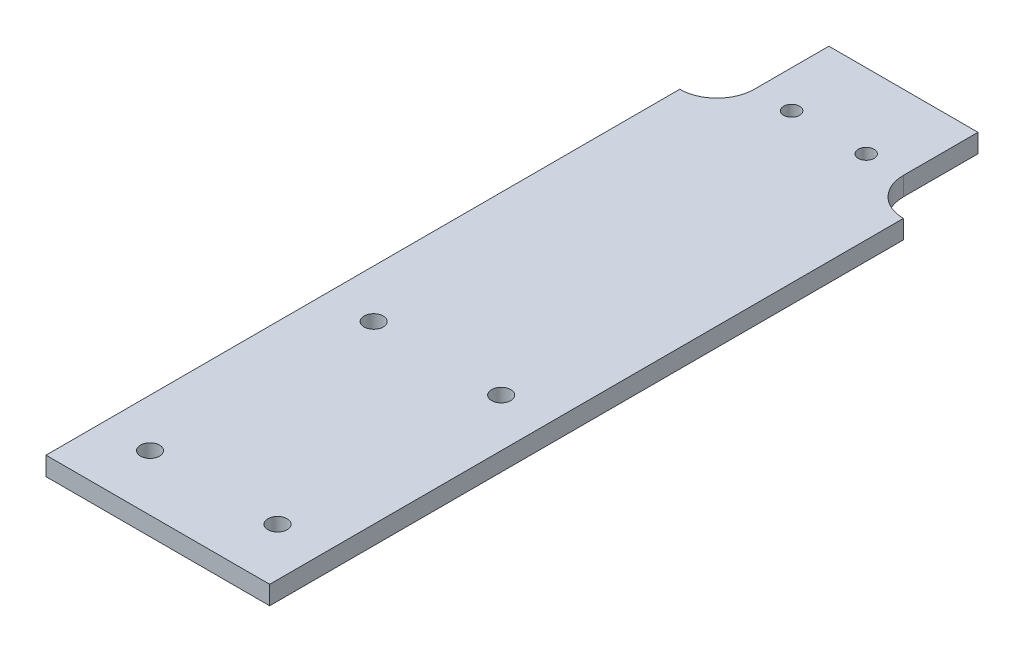
SolidWorks part; units mm, degrees
material "6061 Alloy"
ref_plane "Front Plane" through (0, 0, 0) normal (0, 0, 1) x (1, 0, 0)
ref_plane "Top Plane" through (0, 0, 0) normal (0, 1, 0) x (1, 0, 0)
ref_plane "Right Plane" through (0, 0, 0) normal (1, 0, 0) x (0, 0, -1)
sketch "Sketch1" plane through (0, 0, 0) normal (0, 1, 0) x (1, 0, 0)
  line L1 (-19.05, 50.8) -> (19.05, 50.8)
  line L2 (-19.05, 50.8) -> (-19.05, -76.2)
  line L3 (-19.05, -76.2) -> (19.05, -76.2)
  line L4 (19.05, 50.8) -> (19.05, -76.2)
  dimension "D1" = 38.1
  dimension "D2" = 19.05
  dimension "D3" = 76.2
  dimension "D4" = 50.8
extrude "Extrude1" add sketch "Sketch1" along normal blind 3.175
hole_wizard "#4 Clearance Hole1" positions "3DSketch1" profile "Sketch3" hole size "#4" standard "Ansi Inch"
sketch3d "3DSketch1"
  line L0 (-19.05, 0, 28.575) -> (19.05, 0, 28.575) construction
  line L1 (-19.05, 0, -50.8) -> (-19.05, 0, 76.2) construction
  line L2 (19.05, 0, 76.2) -> (19.05, 0, -50.8) construction
  line L4 (0, 0, 28.575) -> (0, 0, 76.2) construction
  line L5 (-19.05, 0, 76.2) -> (19.05, 0, 76.2) construction
  line L7 (19.05, 0, -50.8) -> (-19.05, 0, -50.8) construction
  line L8 (-19.05, 0, 66.675) -> (19.05, 0, 66.675) construction
  point P0 (-10.8585, 0, 28.575)
  point P2 (10.8585, 0, 28.575)
  point P26 (-10.8585, 0, 66.675)
  point P28 (10.8585, 0, 66.675)
  dimension "D1" = 21.717
  dimension "D2" = 10.8585
  dimension "D3" = 79.375
  dimension "D4" = 38.1
sketch "Sketch3" plane through (-10.8585, 0, 28.575) normal (1, 0, 0) x (0, 0, -1)
  line L0 (0, 0) -> (0, 102.5806)
  line L1 (0, 102.5806) -> (1.6319, 101.6)
  line L2 (1.6319, 101.6) -> (1.6319, 0)
  line L5 (1.6319, 0) -> (0, 0)
  line L10 (0, 102.5806) -> (-1.632, 101.6) construction
  line L11 (0, -6.35) -> (0, 107.95) construction
  dimension "Hole Dia." = 3.2639
  dimension "Hole Depth" = 101.6
  dimension "Drill Angle" = 118
sketch "Sketch4" plane through (0, 0, 0) normal (0, -1, 0) x (1, 0, 0)
  line L1 (-19.05, -50.8) -> (-12.7, -50.8)
  line L2 (-19.05, -50.8) -> (-19.05, -31.75)
  line L3 (-19.05, -31.75) -> (-12.7, -31.75)
  line L4 (-12.7, -50.8) -> (-12.7, -31.75)
  line L5 (19.05, -50.8) -> (12.7, -50.8)
  line L6 (19.05, -50.8) -> (19.05, -31.75)
  line L7 (19.05, -31.75) -> (12.7, -31.75)
  line L8 (12.7, -50.8) -> (12.7, -31.75)
  dimension "D1" = 19.05
  dimension "D2" = 6.35
  dimension "D3" = 6.35
extrude "Cut-Extrude1" cut sketch "Sketch4" against normal through all
hole_wizard "Tap Drill for #6 Tap1" positions "3DSketch2" profile "Sketch5" hole size "#6-32" standard "Ansi Inch"
sketch3d "3DSketch2"
  line L0 (12.7, 3.175, -50.8) -> (-12.7, 3.175, -50.8) construction
  line L1 (12.7, 3.175, -31.75) -> (12.7, 3.175, -50.8) construction
  point P0 (-6.35, 3.175, -38.1)
  point P2 (6.35, 3.175, -38.1)
  dimension "D1" = 12.7
  dimension "D2" = 12.7
  dimension "D3" = 6.35
sketch "Sketch5" plane through (-6.35, 3.175, -38.1) normal (1, 0, 0) x (0, 0, 1)
  line L0 (0, 0) -> (0, 4.1147)
  line L1 (0, 4.1147) -> (1.3525, 3.302)
  line L2 (1.3525, 3.302) -> (1.3525, 0)
  line L5 (1.3525, 0) -> (0, 0)
  line L10 (0, 4.1147) -> (-1.3525, 3.302) construction
  line L11 (0, -6.35) -> (0, 107.95) construction
  dimension "Hole Dia." = 2.7051
  dimension "Hole Depth" = 3.302
  dimension "Drill Angle" = 118
fillet "Fillet1" radius 6.35 2 edges at (-12.7, 1.5875, -31.75) (12.7, 1.5875, -31.75)
